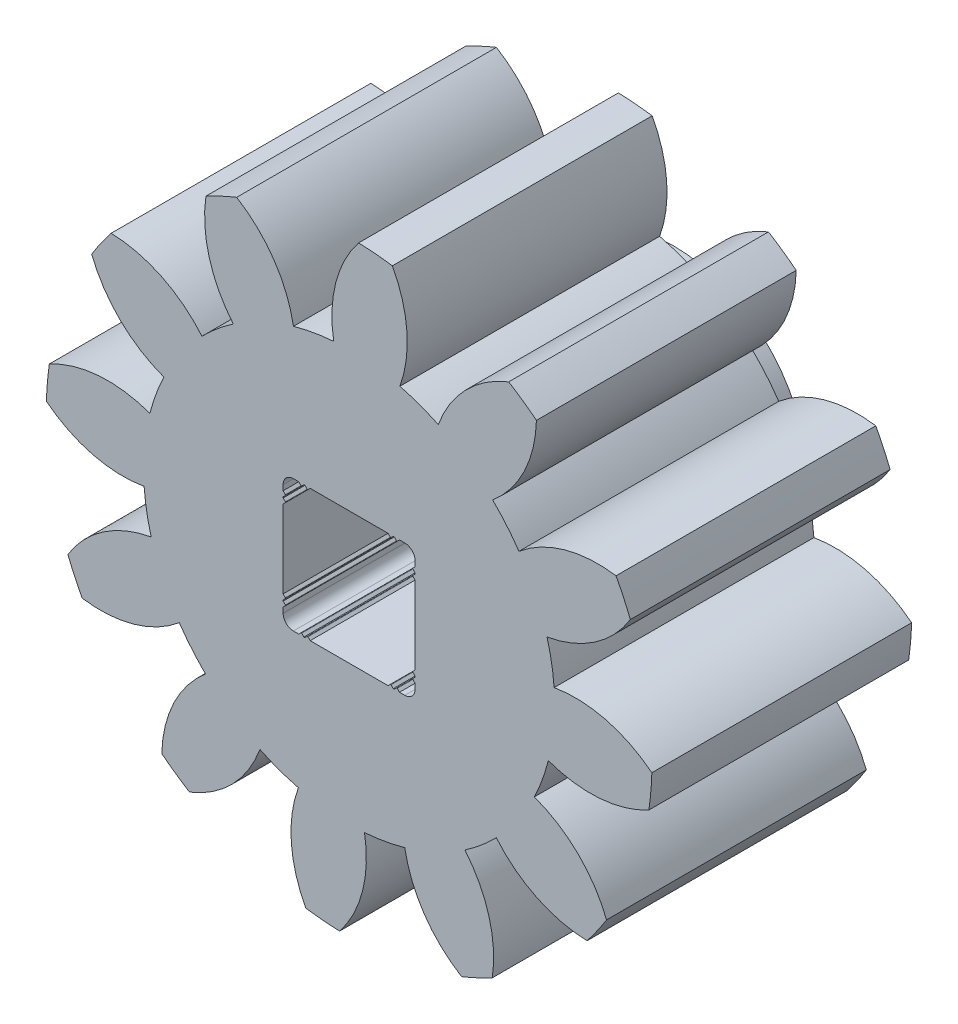
SolidWorks part; units mm, degrees
ref_plane "Front Plane" through (0, 0, 0) normal (0, 0, 1) x (1, 0, 0)
ref_plane "Top Plane" through (0, 0, 0) normal (0, 1, 0) x (1, 0, 0)
ref_plane "Right Plane" through (0, 0, 0) normal (1, 0, 0) x (0, 0, -1)
sketch "Sketch1" plane through (0, 0, 0) normal (0, 1, 0) x (1, 0, 0)
  line L0 (7.404, 3.175) -> (0, 3.175)
  line L1 (0, 3.175) -> (0, -3.175)
  line L2 (0, -3.175) -> (7.404, -3.175)
  line L3 (7.404, -3.175) -> (7.404, 3.175)
  line L4 (0, 3.175) -> (0, -3.175) construction
revolve "Revolve1" add sketch "Sketch1" angle 360 about L4 reverse direction yes
sketch "Sketch2" plane through (0, 0, -3.175) normal (0, 0, -1) x (-1, 0, 0)
  arc A0 (1.057, -7.3282) -> (3.9007, -6.2931) centre (0, 0) ccw
  arc A1 (3.9007, -6.2931) -> (2.1801, -4.528) centre (4.999, -3.5014) cw
  arc A2 (2.1801, -4.528) -> (1.2404, -4.87) centre (0, 0) cw
  arc A3 (1.2404, -4.87) -> (1.057, -7.3282) centre (-1.5788, -5.8955) cw
extrude "Cut-Extrude1" cut sketch "Sketch2" against normal through all
sketch "Sketch3" plane through (0, 0, -3.175) normal (0, 0, -1) x (-1, 0, 0)
  arc A0 (-2.7487, -6.8749) -> (0.2316, -7.4004) centre (0, 0) ccw
  arc A1 (0.2316, -7.4004) -> (-0.3759, -5.0114) centre (2.5786, -5.5318) cw
  arc A2 (-0.3759, -5.0114) -> (-1.3607, -4.8378) centre (0, 0) cw
  arc A3 (-1.3607, -4.8378) -> (-2.7487, -6.8749) centre (-4.3151, -4.3163) cw
extrude "Cut-Extrude2" cut sketch "Sketch3" against normal through all
sketch "Sketch4" plane through (0, 0, -3.175) normal (0, 0, -1) x (-1, 0, 0)
  arc A0 (-5.8179, -4.5795) -> (-3.4996, -6.5247) centre (0, 0) ccw
  arc A1 (-3.4996, -6.5247) -> (-2.8313, -4.152) centre (-0.5328, -6.08) cw
  arc A2 (-2.8313, -4.152) -> (-3.5973, -3.5093) centre (0, 0) cw
  arc A3 (-3.5973, -3.5093) -> (-5.8179, -4.5795) centre (-5.8951, -1.5805) cw
extrude "Cut-Extrude3" cut sketch "Sketch4" against normal through all
sketch "Sketch5" plane through (0, 0, -3.175) normal (0, 0, -1) x (-1, 0, 0)
  arc A0 (-7.3282, -1.057) -> (-6.2931, -3.9007) centre (0, 0) ccw
  arc A1 (-6.2931, -3.9007) -> (-4.528, -2.1801) centre (-3.5014, -4.999) cw
  arc A2 (-4.528, -2.1801) -> (-4.87, -1.2404) centre (0, 0) cw
  arc A3 (-4.87, -1.2404) -> (-7.3282, -1.057) centre (-5.8955, 1.5788) cw
extrude "Cut-Extrude4" cut sketch "Sketch5" against normal through all
sketch "Sketch6" plane through (0, 0, -3.175) normal (0, 0, -1) x (-1, 0, 0)
  arc A0 (-6.8749, 2.7487) -> (-7.4004, -0.2316) centre (0, 0) ccw
  arc A1 (-7.4004, -0.2316) -> (-5.0114, 0.3759) centre (-5.5318, -2.5786) cw
  arc A2 (-5.0114, 0.3759) -> (-4.8378, 1.3607) centre (0, 0) cw
  arc A3 (-4.8378, 1.3607) -> (-6.8749, 2.7487) centre (-4.3163, 4.3151) cw
extrude "Cut-Extrude5" cut sketch "Sketch6" against normal through all
sketch "Sketch7" plane through (0, 0, -3.175) normal (0, 0, -1) x (-1, 0, 0)
  arc A0 (-4.5795, 5.8179) -> (-6.5247, 3.4996) centre (0, 0) ccw
  arc A1 (-6.5247, 3.4996) -> (-4.152, 2.8313) centre (-6.08, 0.5328) cw
  arc A2 (-4.152, 2.8313) -> (-3.5093, 3.5973) centre (0, 0) cw
  arc A3 (-3.5093, 3.5973) -> (-4.5795, 5.8179) centre (-1.5805, 5.8951) cw
extrude "Cut-Extrude6" cut sketch "Sketch7" against normal through all
sketch "Sketch8" plane through (0, 0, -3.175) normal (0, 0, -1) x (-1, 0, 0)
  arc A0 (-1.057, 7.3282) -> (-3.9007, 6.2931) centre (0, 0) ccw
  arc A1 (-3.9007, 6.2931) -> (-2.1801, 4.528) centre (-4.999, 3.5014) cw
  arc A2 (-2.1801, 4.528) -> (-1.2404, 4.87) centre (0, 0) cw
  arc A3 (-1.2404, 4.87) -> (-1.057, 7.3282) centre (1.5788, 5.8955) cw
extrude "Cut-Extrude7" cut sketch "Sketch8" against normal through all
sketch "Sketch9" plane through (0, 0, -3.175) normal (0, 0, -1) x (-1, 0, 0)
  arc A0 (2.7487, 6.8749) -> (-0.2316, 7.4004) centre (0, 0) ccw
  arc A1 (-0.2316, 7.4004) -> (0.3759, 5.0114) centre (-2.5786, 5.5318) cw
  arc A2 (0.3759, 5.0114) -> (1.3607, 4.8378) centre (0, 0) cw
  arc A3 (1.3607, 4.8378) -> (2.7487, 6.8749) centre (4.3151, 4.3163) cw
extrude "Cut-Extrude8" cut sketch "Sketch9" against normal through all
sketch "Sketch10" plane through (0, 0, -3.175) normal (0, 0, -1) x (-1, 0, 0)
  arc A0 (5.8179, 4.5795) -> (3.4996, 6.5247) centre (0, 0) ccw
  arc A1 (3.4996, 6.5247) -> (2.8313, 4.152) centre (0.5328, 6.08) cw
  arc A2 (2.8313, 4.152) -> (3.5973, 3.5093) centre (0, 0) cw
  arc A3 (3.5973, 3.5093) -> (5.8179, 4.5795) centre (5.8951, 1.5805) cw
extrude "Cut-Extrude9" cut sketch "Sketch10" against normal through all
sketch "Sketch11" plane through (0, 0, -3.175) normal (0, 0, -1) x (-1, 0, 0)
  arc A0 (7.3282, 1.057) -> (6.2931, 3.9007) centre (0, 0) ccw
  arc A1 (6.2931, 3.9007) -> (4.528, 2.1801) centre (3.5014, 4.999) cw
  arc A2 (4.528, 2.1801) -> (4.87, 1.2404) centre (0, 0) cw
  arc A3 (4.87, 1.2404) -> (7.3282, 1.057) centre (5.8955, -1.5788) cw
extrude "Cut-Extrude10" cut sketch "Sketch11" against normal through all
sketch "Sketch12" plane through (0, 0, -3.175) normal (0, 0, -1) x (-1, 0, 0)
  arc A0 (6.8749, -2.7487) -> (7.4004, 0.2316) centre (0, 0) ccw
  arc A1 (7.4004, 0.2316) -> (5.0114, -0.3759) centre (5.5318, 2.5786) cw
  arc A2 (5.0114, -0.3759) -> (4.8378, -1.3607) centre (0, 0) cw
  arc A3 (4.8378, -1.3607) -> (6.8749, -2.7487) centre (4.3163, -4.3151) cw
extrude "Cut-Extrude11" cut sketch "Sketch12" against normal through all
sketch "Sketch13" plane through (0, 0, -3.175) normal (0, 0, -1) x (-1, 0, 0)
  arc A0 (4.5795, -5.8179) -> (6.5247, -3.4996) centre (0, 0) ccw
  arc A1 (6.5247, -3.4996) -> (4.152, -2.8313) centre (6.08, -0.5328) cw
  arc A2 (4.152, -2.8313) -> (3.5093, -3.5973) centre (0, 0) cw
  arc A3 (3.5093, -3.5973) -> (4.5795, -5.8179) centre (1.5805, -5.8951) cw
extrude "Cut-Extrude12" cut sketch "Sketch13" against normal through all
sketch "Sketch14" plane through (0, 0, 3.175) normal (0, 0, 1) x (1, 0, 0)
  circle A0 centre (0, 0) radius 3.25
sketch "Sketch15" plane through (0, 0, -3.175) normal (0, 0, -1) x (-1, 0, 0)
  circle A0 centre (0, 0) radius 3.25
extrude "Boss-Extrude2" add sketch "Sketch15" along normal blind 1.5875
sketch "Sketch16" plane through (0, 0, -4.7625) normal (0, 0, -1) x (-1, 0, 0)
  line L0 (1.5488, 1.1682) -> (1.6125, 1.2315)
  line L1 (1.6125, 1.2315) -> (1.6125, 1.6125)
  line L2 (1.6125, 1.6125) -> (1.2315, 1.6125)
  line L3 (1.2315, 1.6125) -> (1.168, 1.549)
  line L4 (1.168, 1.549) -> (1.0918, 1.6252)
  line L5 (1.0918, 1.6252) -> (1.0156, 1.549)
  line L6 (1.0156, 1.549) -> (0.9521, 1.6125)
  line L7 (0.9521, 1.6125) -> (-0.9521, 1.6125)
  line L8 (-0.9521, 1.6125) -> (-1.0156, 1.5488)
  line L9 (-1.0156, 1.5488) -> (-1.0918, 1.6252)
  line L10 (-1.0918, 1.6252) -> (-1.168, 1.5488)
  line L11 (-1.168, 1.5488) -> (-1.2315, 1.6125)
  line L12 (-1.2315, 1.6125) -> (-1.6125, 1.6125)
  line L13 (-1.6125, 1.6125) -> (-1.6125, 1.2315)
  line L14 (-1.6125, 1.2315) -> (-1.5488, 1.168)
  line L15 (-1.5488, 1.168) -> (-1.6252, 1.0918)
  line L16 (-1.6252, 1.0918) -> (-1.5488, 1.0156)
  line L17 (-1.5488, 1.0156) -> (-1.6125, 0.9521)
  line L18 (-1.6125, 0.9521) -> (-1.6125, -0.9521)
  line L19 (-1.6125, -0.9521) -> (-1.549, -1.0156)
  line L20 (-1.549, -1.0156) -> (-1.6252, -1.0918)
  line L21 (-1.6252, -1.0918) -> (-1.5488, -1.1682)
  line L22 (-1.5488, -1.1682) -> (-1.6125, -1.2315)
  line L23 (-1.6125, -1.2315) -> (-1.6125, -1.6125)
  line L24 (-1.6125, -1.6125) -> (-1.2315, -1.6125)
  line L25 (-1.2315, -1.6125) -> (-1.168, -1.549)
  line L26 (-1.168, -1.549) -> (-1.0918, -1.6252)
  line L27 (-1.0918, -1.6252) -> (-1.0156, -1.549)
  line L28 (-1.0156, -1.549) -> (-0.9521, -1.6125)
  line L29 (-0.9521, -1.6125) -> (0.9521, -1.6125)
  line L30 (0.9521, -1.6125) -> (1.0156, -1.5488)
  line L31 (1.0156, -1.5488) -> (1.0918, -1.6252)
  line L32 (1.0918, -1.6252) -> (1.168, -1.5488)
  line L33 (1.168, -1.5488) -> (1.2315, -1.6125)
  line L34 (1.2315, -1.6125) -> (1.6125, -1.6125)
  line L35 (1.6125, -1.6125) -> (1.6125, -1.2315)
  line L36 (1.6125, -1.2315) -> (1.5488, -1.168)
  line L37 (1.5488, -1.168) -> (1.6252, -1.0918)
  line L38 (1.6252, -1.0918) -> (1.5488, -1.0156)
  line L39 (1.5488, -1.0156) -> (1.6125, -0.9521)
  line L40 (1.6125, -0.9521) -> (1.6125, 0.9521)
  line L41 (1.6125, 0.9521) -> (1.549, 1.0156)
  line L42 (1.549, 1.0156) -> (1.6252, 1.0918)
  line L43 (1.6252, 1.0918) -> (1.5488, 1.1682)
extrude "Cut-Extrude13" cut sketch "Sketch16" against normal through all
fillet "Fillet1" radius 0.0127 16 edges at (1.168, -1.549, -0.7938) (-1.168, 1.549, -0.7938) (1.5488, 1.0156, -0.7938) (1.5488, 1.168, -0.7938) (-1.0156, 1.549, -0.7938) (1.168, 1.5488, -0.7938) (1.5488, -1.1682, -0.7938) (-1.168, -1.5488, -0.7938) (1.0156, 1.5488, -0.7938) (-1.0156, -1.5488, -0.7938) (1.549, -1.0156, -0.7938) (1.0156, -1.549, -0.7938) (-1.5488, -1.0156, -0.7938) (-1.549, 1.0156, -0.7938) (-1.5488, 1.1682, -0.7938) (-1.5488, -1.168, -0.7938) tangent propagation no
chamfer "Chamfer1" distance 0.018 angle 45 4 edges at (1.0918, -1.6252, -0.7938) (-1.0918, 1.6252, -0.7938) (1.6252, -1.0918, -0.7938) (-1.6252, 1.0918, -0.7938)
chamfer "Chamfer2" distance 0.018 angle 45.095 4 edges at (1.6252, 1.0918, -0.7938) (-1.0918, -1.6252, -0.7938) (-1.6252, -1.0918, -0.7938) (1.0918, 1.6252, -0.7938) first distance on face at (1.5915, 1.0582, -0.7938) first distance on face at (-1.1254, -1.5915, -0.7938) first distance on face at (-1.5915, -1.0582, -0.7938) first distance on face at (1.1254, 1.5915, -0.7938)
fillet "Fillet2" radius 0.25 4 edges at (-1.6125, -1.6125, -0.7938) (1.6125, 1.6125, -0.7938) (-1.6125, 1.6125, -0.7938) (1.6125, -1.6125, -0.7938) tangent propagation no
